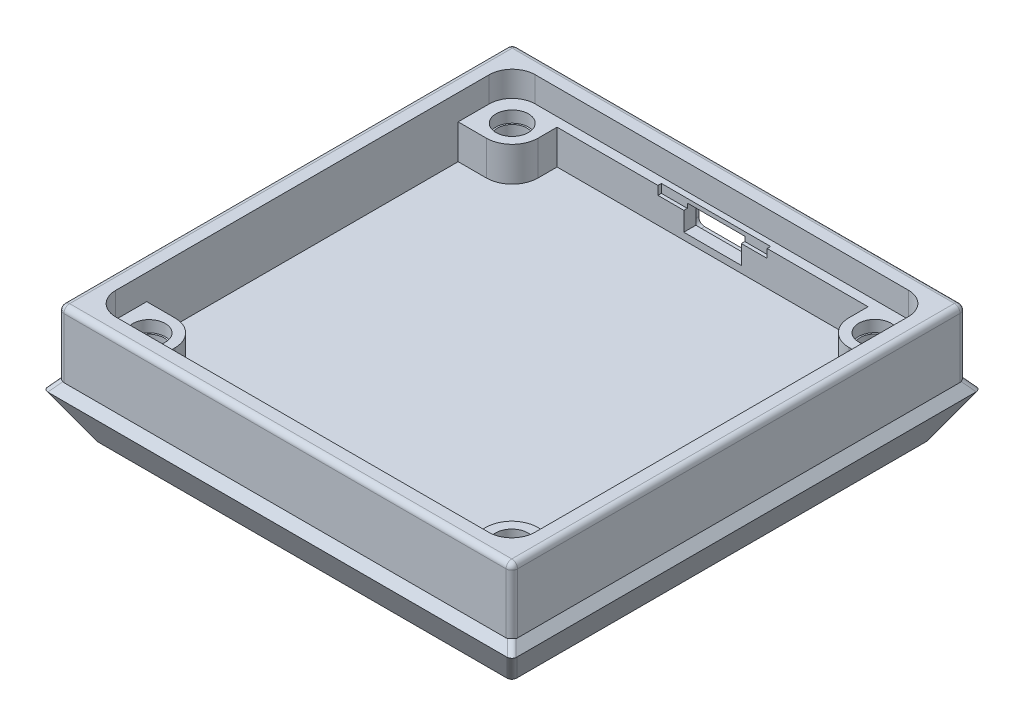
SolidWorks part; units mm, degrees
ref_plane "Front Plane" through (0, 0, 0) normal (0, 0, 1) x (1, 0, 0)
ref_plane "Top Plane" through (0, 0, 0) normal (0, 1, 0) x (1, 0, 0)
ref_plane "Right Plane" through (0, 0, 0) normal (1, 0, 0) x (0, 0, -1)
sketch "Sketch1" plane through (0, 0, 0) normal (0, 1, 0) x (1, 0, 0)
  line L0 (-34.54, 34.575) -> (-34.54, 36.475) construction
  line L1 (-34.54, -34.575) -> (34.54, -34.575)
  line L2 (-34.54, -34.575) -> (-34.54, 34.575)
  line L3 (-34.54, 34.575) -> (34.54, 34.575)
  line L4 (34.54, -34.575) -> (34.54, 34.575)
  line L5 (-34.54, -34.575) -> (34.54, 34.575) construction
  line L6 (-34.54, 34.575) -> (34.54, -34.575) construction
  line L7 (-34.54, 36.475) -> (-36.44, 36.475) construction
  line L8 (34.54, -34.575) -> (36.44, -34.575) construction
  line L9 (36.44, -34.575) -> (36.44, -36.475) construction
  line L11 (-36.44, 36.475) -> (36.44, 36.475)
  line L12 (-36.44, 36.475) -> (-36.44, -36.475)
  line L13 (-36.44, -36.475) -> (36.44, -36.475)
  line L14 (36.44, 36.475) -> (36.44, -36.475)
  point P0 (0, 0)
  dimension "D1" = 69.15
  dimension "D2" = 69.08
  dimension "D3" = 1.9
  dimension "D4" = 1.9
  dimension "D5" = 1.9
  dimension "D6" = 1.9
extrude "floor" add sketch "Sketch1" along normal blind 10 contours L14 L11 L12 L13 L4 L1 L2 L3 | L1 L4 L3 L2 region at (0, 0, 0) region at (0, 0, -35.4438)
sketch "Sketch3" plane through (0, 0, 0) normal (0, -1, 0) x (1, 0, 0)
  line L0 (36.44, 36.475) -> (39.44, 36.475) construction
  line L1 (39.44, 36.475) -> (39.44, 39.475) construction
  line L2 (-36.44, -36.475) -> (-39.44, -36.475) construction
  line L3 (-39.44, -36.475) -> (-39.44, -39.475) construction
  line L5 (-39.44, -39.475) -> (39.44, -39.475)
  line L6 (-39.44, -39.475) -> (-39.44, 39.475)
  line L7 (-39.44, 39.475) -> (39.44, 39.475)
  line L8 (39.44, -39.475) -> (39.44, 39.475)
  line L9 (-36.44, 36.475) -> (36.44, 36.475)
  line L10 (-36.44, 36.475) -> (-36.44, -36.475)
  line L11 (-36.44, -36.475) -> (36.44, -36.475)
  line L12 (36.44, 36.475) -> (36.44, -36.475)
  dimension "D1" = 3
  dimension "D2" = 3
  dimension "D3" = 3
  dimension "D4" = 3
extrude "walls from bottom" add sketch "Sketch3" against normal blind 20.4
sketch "Sketch4" plane through (0, 10, 0) normal (0, 1, 0) x (1, 0, 0)
  line L0 (-34.5375, 34.575) -> (-31.5375, 34.575) construction
  line L1 (-34.5375, -34.575) -> (34.5375, -34.575) construction
  line L2 (-34.5375, -34.575) -> (-34.5375, 34.575) construction
  line L3 (-34.5375, 34.575) -> (34.5375, 34.575) construction
  line L4 (34.5375, -34.575) -> (34.5375, 34.575) construction
  line L5 (-34.5375, -34.575) -> (34.5375, 34.575) construction
  line L6 (-34.5375, 34.575) -> (34.5375, -34.575) construction
  line L7 (-31.5375, 34.575) -> (-31.5375, 31.575) construction
  line L8 (34.5375, -34.575) -> (31.5375, -34.575) construction
  line L9 (31.5375, -34.575) -> (31.5375, -31.575) construction
  line L10 (-31.5375, -27.075) -> (-36.44, -27.075)
  line L11 (-31.5375, 31.575) -> (31.5375, 31.575) construction
  line L12 (-31.5375, 31.575) -> (-31.5375, -31.575) construction
  line L13 (-31.5375, -31.575) -> (31.5375, -31.575) construction
  line L14 (31.5375, 31.575) -> (31.5375, -31.575) construction
  line L15 (-36.44, -36.475) -> (-36.44, 36.475) construction
  line L16 (-27.0375, 31.575) -> (-27.0375, 36.475)
  line L17 (36.44, -36.475) -> (-36.44, -36.475) construction
  line L18 (-36.44, 36.475) -> (36.44, 36.475) construction
  line L19 (31.5375, -27.075) -> (36.44, -27.075)
  line L22 (31.5375, 27.075) -> (36.44, 27.075)
  line L23 (36.44, 36.475) -> (36.44, -36.475) construction
  line L24 (-27.0375, 36.475) -> (-31.5375, 36.475)
  line L25 (-36.44, 36.475) -> (36.44, 36.475) construction
  line L26 (-31.5375, 27.075) -> (-36.44, 27.075)
  line L27 (27.0375, 31.575) -> (27.0375, 36.475)
  line L28 (-36.44, 27.075) -> (-36.44, 36.475)
  line L29 (-36.44, 36.475) -> (-31.5375, 36.475)
  line L30 (31.5375, 36.475) -> (36.44, 36.475)
  line L31 (36.44, 36.475) -> (36.44, 27.075)
  line L32 (31.5375, -36.475) -> (36.44, -36.475)
  line L33 (36.44, -36.475) -> (36.44, -27.075)
  line L34 (-36.44, -27.075) -> (-36.44, -36.475)
  line L35 (-27.0375, -36.475) -> (-36.44, -36.475)
  line L36 (27.0375, 36.475) -> (31.5375, 36.475)
  line L37 (27.0375, -31.575) -> (27.0375, -36.475)
  line L40 (27.0375, -36.475) -> (31.5375, -36.475)
  line L41 (-27.0375, -31.575) -> (-27.0375, -36.475)
  circle A8 centre (-31.5375, 31.575) radius 2.55
  circle A9 centre (31.5375, 31.575) radius 4.5
  circle A10 centre (31.5375, -31.575) radius 2.55
  circle A11 centre (-31.5375, -31.575) radius 4.5
  circle A12 centre (-31.5375, -31.575) radius 2.55
  circle A13 centre (-31.5375, 31.575) radius 4.5
  circle A14 centre (31.5375, -31.575) radius 4.5
  circle A15 centre (31.5375, 31.575) radius 2.55
  point P0 (0, 0)
  line M5 (36.44, -36.475) -> (36.44, 36.475)
  line M6 (36.44, 36.475) -> (-36.44, 36.475)
  line M7 (-36.44, 36.475) -> (-36.44, -36.475)
  line M8 (-36.44, -36.475) -> (36.44, -36.475)
  dimension "D3" = 3
  dimension "D4" = 3
  dimension "D7" = 5.1
  dimension "D8" = 9
  dimension "D9" = 5.1
  dimension "D10" = 9
  dimension "D11" = 5.1
  dimension "D12" = 9
  dimension "D13" = 5.1
  dimension "D14" = 9
  dimension "D1" = 69.075
  dimension "D2" = 69.15
  dimension "D5" = 3
  dimension "D6" = 3
extrude "Boss-Extrude1" add sketch "Sketch4" along normal blind 6 contours A13 L26 M6 M7 | A9 L22 M5 M6 | A14 L19 M8 M5 | A11 L10 M7 M8 | A11 A12 | A13 A8 | A9 A15 | A14 A10 region at (-34.8135, 10, 34.851) region at (-28.4455, 10, 28.483) region at (-36.307, 10, -31.775) region at (-34.6295, 10, -34.667) region at (27.1705, 10, 34.025) region at (28.4455, 10, 28.483) region at (29.2875, 10, -36.342) region at (31.5375, 10, -35.9477)
sketch "Sketch21" plane through (0, 16, 0) normal (0, 1, 0) x (1, 0, 0)
  circle A0 centre (-31.5375, 31.575) radius 2.825
  circle A1 centre (31.5375, 31.575) radius 2.825
  circle A2 centre (-31.5375, -31.575) radius 2.825
  circle A3 centre (31.5375, -31.575) radius 2.825
  dimension "D1" = 5.65
  dimension "D2" = 5.65
  dimension "D3" = 5.65
  dimension "D4" = 5.65
extrude "Cut-Extrude9" cut sketch "Sketch21" against normal blind 2
sketch "Sketch7" plane through (0, 16, 0) normal (0, 1, 0) x (1, 0, 0)
  line L0 (-31.5375, 31.575) -> (-31.5375, 34.575) construction
  line L1 (-31.5375, 34.575) -> (-31.5375, 34.875) construction
  line L2 (-31.5375, 34.875) -> (31.5375, 34.875) construction
  line L3 (31.5375, 31.575) -> (31.5375, 34.875) construction
  line L4 (-27.0375, 36.475) -> (-27.0375, 34.875)
  line L5 (-27.0375, 31.575) -> (-27.0375, 36.475) construction
  line L6 (27.0375, 36.475) -> (27.0375, 34.875)
  line L7 (27.0375, 31.575) -> (27.0375, 36.475) construction
  line L8 (-27.0375, 34.875) -> (27.0375, 34.875)
  line L9 (-27.0375, 36.475) -> (27.0375, 36.475)
  dimension "D1" = 3
  dimension "D2" = 0.3
extrude "Boss-Extrude2" add sketch "Sketch7" against normal up to surface (6 mm away) up to face at (0, 10, 0)
sketch "Sketch8" plane through (0, 16, 0) normal (0, 1, 0) x (1, 0, 0)
  line L0 (-36.44, 36.475) -> (36.44, 36.475) construction
  line L1 (0, 36.475) -> (0, 34.875) construction
  line L2 (27.0375, 34.875) -> (-27.0375, 34.875) construction
  line L3 (0, 34.875) -> (-5, 34.875)
  line L5 (0, 34.875) -> (5, 34.875)
  line L6 (-5, 34.875) -> (-5, 36.475)
  line L7 (-5, 36.475) -> (0, 36.475)
  line L8 (0, 36.475) -> (5, 36.475)
  line L9 (5, 36.475) -> (5, 34.875)
  point P11 (0, 34.875)
  point P13 (0, 35.575)
  dimension "D1" = 5
  dimension "D2" = 5
extrude "Cut-Extrude1" cut sketch "Sketch8" against normal blind 4.8 contours L9 L5 L3 L6 L7 L8
sketch "Sketch9" plane through (0, 0, -36.475) normal (0, 0, 1) x (1, 0, 0)
  line L0 (0, 11.2) -> (0, 15.3) construction
  line L1 (-5, 11.2) -> (5, 11.2) construction
  line L2 (0, 15.3) -> (-5, 15.3)
  line L3 (-5, 11.2) -> (-5, 16) construction
  line L4 (0, 15.3) -> (5, 15.3)
  line L5 (5, 11.2) -> (5, 16) construction
  line L6 (-5, 15.3) -> (-5, 11.2)
  line L7 (-5, 11.2) -> (5, 11.2)
  line L8 (5, 11.2) -> (5, 15.3)
  dimension "D1" = 4.1
extrude "Cut-Extrude2" cut sketch "Sketch9" against normal through all
sketch "Sketch10" plane through (0, 16, 0) normal (0, 1, 0) x (1, 0, 0)
  line L0 (-5, 34.875) -> (-5, 36.475) construction
  line L1 (-5, 34.875) -> (-9.5, 34.875)
  line L2 (-5, 34.875) -> (-5, 36.475)
  line L3 (-5, 36.475) -> (-9.5, 36.475)
  line L4 (-9.5, 34.875) -> (-9.5, 36.475)
  line L5 (-27.0375, 34.875) -> (-5, 34.875) construction
  line L6 (-36.44, 36.475) -> (36.44, 36.475) construction
  line L7 (36.44, 36.475) -> (5, 36.475) construction
  line L8 (5, 34.875) -> (9.5, 34.875)
  line L9 (5, 34.875) -> (5, 36.475)
  line L10 (5, 36.475) -> (9.5, 36.475)
  line L11 (9.5, 34.875) -> (9.5, 36.475)
  dimension "D1" = 4.5
  dimension "D2" = 4.5
extrude "Cut-Extrude3" cut sketch "Sketch10" against normal blind 1.5
sketch "Sketch11" plane through (0, 0, -39.475) normal (0, 0, -1) x (-1, 0, 0)
  line L0 (-5, 15.3) -> (5, 11.2) construction
  line L1 (5, 15.3) -> (-5, 11.2) construction
  line L2 (0, 9.25) -> (0, 17.25) construction
  line L3 (-6, 17.25) -> (6, 17.25)
  line L4 (-6, 9.25) -> (6, 9.25)
  line L5 (-7, 16.25) -> (-7, 10.25)
  line L6 (7, 16.25) -> (7, 10.25)
  arc A0 (-6, 9.25) -> (-7, 10.25) centre (-6, 10.25) cw
  arc A1 (6, 9.25) -> (7, 10.25) centre (6, 10.25) ccw
  arc A2 (6, 17.25) -> (7, 16.25) centre (6, 16.25) cw
  arc A3 (-6, 17.25) -> (-7, 16.25) centre (-6, 16.25) ccw
  point P12 (0, 13.25)
  point P15 (0, 17.25)
  point P18 (0, 9.25)
  point P20 (-7, 9.25)
  point P23 (7, 9.25)
  point P26 (7, 17.25)
  dimension "D3" = 1
  dimension "D1" = 8
  dimension "D2" = 14
extrude "Cut-Extrude4" cut sketch "Sketch11" against normal blind 2.5
sketch "Sketch16" plane through (0, 0, -39.475) normal (0, 0, -1) x (-1, 0, 0)
  line L0 (-39.44, 20.4) -> (-39.44, 0) construction
  line L1 (39.44, 0) -> (39.44, 20.4) construction
  line L2 (-39.44, 9) -> (-46.665, 9)
  line L3 (-46.665, 9) -> (-46.665, 0)
  line L4 (-46.665, 0) -> (44.9933, 0)
  line L5 (44.9933, 0) -> (44.9933, 9)
  line L6 (44.9933, 9) -> (-39.44, 9)
  line L7 (-39.44, 20.4) -> (-39.44, 0) construction
  dimension "D1" = 9
extrude "Boss-Extrude7" add sketch "Sketch16" against normal blind 87
sketch "Sketch17" plane through (46.665, 0, 0) normal (1, 0, 0) x (0, 0, -1)
  line L1 (39.475, 0) -> (43.2265, 0)
  line L2 (39.475, 0) -> (39.475, 9)
  line L3 (39.475, 9) -> (43.2265, 9)
  line L4 (43.2265, 0) -> (43.2265, 9)
extrude "Boss-Extrude8" add sketch "Sketch17" against normal up to surface (91.6583 mm away) up to face at (-44.9933, 4.5, 4.025)
sketch "Sketch19" plane through (0, 0, -43.2265) normal (0, 0, -1) x (-1, 0, 0)
  line L0 (-39.44, 9) -> (-40.7256, 7.4679)
  line L1 (-40.7256, 7.4679) -> (-36.414, 0)
  line L2 (44.9933, 0) -> (-46.665, 0) construction
  line L3 (-39.44, 20.4) -> (-39.44, 9) construction
  line L4 (-36.414, 0) -> (-50.6273, 0)
  line L5 (-50.6273, 0) -> (-50.6273, 9)
  line L6 (-50.6273, 9) -> (-39.44, 9)
  line L7 (39.44, 9) -> (40.7256, 7.4679)
  line L8 (40.7256, 7.4679) -> (36.414, 0)
  line L9 (39.44, 20.4) -> (39.44, 9) construction
  line L10 (36.414, 0) -> (59.329, 0)
  line L11 (59.329, 0) -> (59.329, 9)
  line L12 (59.329, 9) -> (39.44, 9)
  dimension "D1" = 2
  dimension "D2" = 140
  dimension "D3" = 110
  dimension "D4" = 140
  dimension "D5" = 110
  dimension "D6" = 2
extrude "Cut-Extrude7" cut sketch "Sketch19" against normal through all both
sketch "Sketch20" plane through (39.44, 0, 0) normal (1, 0, 0) x (0, 0, -1)
  line L0 (-39.475, 9) -> (-40.7606, 7.4679)
  line L1 (-47.525, 7.4679) -> (43.2265, 7.4679) construction
  line L2 (-40.7606, 7.4679) -> (-36.449, 0)
  line L3 (-47.525, 0) -> (43.2265, 0) construction
  line L4 (-39.475, 20.4) -> (-39.475, 9) construction
  line L5 (39.475, 9) -> (40.7606, 7.4679)
  line L6 (40.7606, 7.4679) -> (36.449, 0)
  line L7 (39.475, 20.4) -> (39.475, 9) construction
  line L8 (-36.449, 0) -> (-51.4465, 0)
  line L9 (-51.4465, 0) -> (-51.4465, 9)
  line L10 (-51.4465, 9) -> (-39.475, 9)
  line L11 (39.475, 9) -> (51.5191, 9)
  line L12 (51.5191, 9) -> (51.5191, 0)
  line L13 (51.5191, 0) -> (36.449, 0)
  dimension "D1" = 140
  dimension "D2" = 110
  dimension "D3" = 140
  dimension "D4" = 110
extrude "Cut-Extrude8" cut sketch "Sketch20" against normal through all both and the other way blind 39
fillet "Fillet1" radius 4 4 edges at (-36.44, 18.2, 36.475) (36.44, 18.2, 36.475) (36.44, 18.2, -36.475) (-36.44, 18.2, -36.475)
fillet "Fillet2" radius 1 12 edges at (38.5698, 3.734, -38.6048) (40.0828, 8.234, -40.1178) (39.44, 14.7, -39.475) (-39.44, 14.7, -39.475) (-40.0828, 8.234, -40.1178) (-38.5698, 3.734, -38.6048) (-38.5698, 3.734, 38.6048) (-40.0828, 8.234, 40.1178) (38.5698, 3.734, 38.6048) (40.0828, 8.234, 40.1178) (39.44, 14.7, 39.475) (-39.44, 14.7, 39.475)
fillet "Fillet3" radius 1 8 edges at (39.1471, 20.4, 39.1821) (39.44, 20.4, 0) (39.1471, 20.4, -39.1821) (0, 20.4, -39.475) (-39.1471, 20.4, -39.1821) (-39.44, 20.4, 0) (-39.1471, 20.4, 39.1821) (0, 20.4, 39.475)
sketch "plate export" plane through (0, 16, 0) normal (0, 1, 0) x (1, 0, 0)
  line L12 (-36.54, 32.575) -> (-36.54, -32.575)
  line L13 (32.54, -36.575) -> (-32.54, -36.575)
  line L14 (36.54, 32.575) -> (36.54, -32.575)
  line L15 (32.54, 36.575) -> (-32.54, 36.575)
  line L16 (0, -36.575) -> (0, -27.2079)
  line L17 (-7.4554, -27.2079) -> (7.4554, -27.2079)
  line L18 (-7.4554, -10.6929) -> (7.4554, -10.6929)
  line L19 (-7.4554, -10.6929) -> (-7.4554, -27.2079)
  line L20 (7.4554, -10.6929) -> (7.4554, -27.2079)
  line L21 (-7.4554, -18.9504) -> (-11.7304, -18.9504) construction
  line L22 (-7.4554, -10.6929) -> (-11.7304, -10.6929) construction
  line L23 (-7.4554, -27.2079) -> (-11.7304, -27.2079) construction
  line L24 (7.4554, -10.6929) -> (11.7491, -10.6929) construction
  line L25 (-11.7304, -27.2079) -> (-26.5137, -27.2079)
  line L26 (-11.7304, -27.2079) -> (-11.7304, -10.6929)
  line L27 (-11.7304, -10.6929) -> (-26.5137, -10.6929)
  line L28 (-26.5137, -27.2079) -> (-26.5137, -10.6929)
  line L29 (7.4554, -27.2079) -> (11.7491, -27.2079) construction
  line L30 (11.7491, -10.6929) -> (11.7491, -8.1385) construction
  line L31 (11.7491, -27.2079) -> (26.3694, -27.2079)
  line L32 (11.7491, -27.2079) -> (11.7491, -10.6929)
  line L33 (11.7491, -10.6929) -> (26.3694, -10.6929)
  line L34 (26.3694, -27.2079) -> (26.3694, -10.6929)
  line L35 (26.3694, -10.6929) -> (26.3694, -8.1385) construction
  line L36 (7.4554, -10.6929) -> (7.4554, -8.1385) construction
  line L37 (11.7491, -8.1385) -> (26.3694, -8.1385)
  line L38 (11.7491, -8.1385) -> (11.7491, 8.1667)
  line L39 (11.7491, 8.1667) -> (26.3694, 8.1667)
  line L40 (26.3694, -8.1385) -> (26.3694, 8.1667)
  line L41 (-26.5137, -10.6929) -> (-26.5137, -8.1385) construction
  line L42 (-11.7304, -10.6929) -> (-11.7304, -8.1385) construction
  line L43 (-11.7304, -8.1385) -> (-7.4554, -8.1385) construction
  line L44 (-26.5137, -8.1385) -> (-11.7304, -8.1385)
  line L45 (-26.5137, -8.1385) -> (-26.5137, 8.1667)
  line L46 (-26.5137, 8.1667) -> (-11.7304, 8.1667)
  line L47 (-11.7304, -8.1385) -> (-11.7304, 8.1667)
  line L48 (11.7491, 8.1667) -> (7.4554, 8.1667) construction
  line L49 (21.5375, 11.575) -> (21.5375, 11.275) construction
  line L50 (-7.4554, -8.1385) -> (7.4554, -8.1385)
  line L51 (-7.4554, -8.1385) -> (-7.4554, 8.1667)
  line L52 (-7.4554, 8.1667) -> (7.4554, 8.1667)
  line L53 (7.4554, -8.1385) -> (7.4554, 8.1667)
  line L54 (21.5375, 11.275) -> (25.6875, 11.275) construction
  line L55 (25.3875, 19.075) -> (25.6875, 19.075) construction
  line L56 (-25.7125, 27.7874) -> (-31.5375, 27.7874) construction
  line L57 (25.6875, 19.075) -> (25.6875, 11.275) construction
  line L58 (25.3875, 19.725) -> (25.3875, 18.425) construction
  line L59 (-21.5625, 12.1) -> (-21.5625, 11.8) construction
  line L60 (25.6875, 11.275) -> (12.4598, 11.275)
  line L61 (25.6875, 11.275) -> (25.6875, 27.189)
  line L62 (25.6875, 27.189) -> (12.4598, 27.189)
  line L63 (12.4598, 11.275) -> (12.4598, 27.189)
  line L64 (-25.4125, 19.6) -> (-25.7125, 19.6) construction
  line L65 (-25.4125, 18.95) -> (-25.4125, 20.25) construction
  line L66 (-25.7125, 19.6) -> (-25.7125, 11.8) construction
  line L67 (-25.7125, 11.8) -> (-21.5625, 11.8) construction
  line L68 (-31.5375, 27.7874) -> (-31.5375, 31.575) construction
  line L69 (-25.7125, 11.8) -> (-12.5037, 11.8)
  line L70 (-25.7125, 11.8) -> (-25.7125, 27.7874)
  line L71 (-25.7125, 27.7874) -> (-12.5037, 27.7874)
  line L72 (-12.5037, 11.8) -> (-12.5037, 27.7874)
  line L73 (-31.5375, 31.575) -> (31.5375, 31.575) construction
  circle A0 centre (21.5375, 12.075) radius 0.5 construction
  circle A1 centre (-21.5625, 12.6) radius 0.5 construction
  arc A2 (-32.54, -36.575) -> (-36.54, -32.575) centre (-32.54, -32.575) cw
  arc A3 (36.54, -32.575) -> (32.54, -36.575) centre (32.54, -32.575) cw
  arc A4 (32.54, 36.575) -> (36.54, 32.575) centre (32.54, 32.575) cw
  arc A5 (-36.54, 32.575) -> (-32.54, 36.575) centre (-32.54, 32.575) cw
  point P12 (0, -27.2079)
  point P17 (0, -10.6929)
  dimension "D1" = 4
sketch "Sketch22" plane through (0, 0, -36.475) normal (0, 0, 1) x (1, 0, 0)
  line L0 (-9.5, 16) -> (9.5, 16)
  line L1 (9.5, 16) -> (9.5, 14.5)
  line L2 (9.5, 14.5) -> (5, 14.5)
  line L3 (5, 14.5) -> (5, 15.3)
  line L4 (5, 15.3) -> (-5, 15.3)
  line L5 (-5, 15.3) -> (-5, 14.5)
  line L6 (-5, 14.5) -> (-9.5, 14.5)
  line L7 (-9.5, 14.5) -> (-9.5, 16)
extrude "Boss-Extrude9" add sketch "Sketch22" along normal blind 1
equation "\"D4@Sketch1\"= \"D3@Sketch1\""
equation "\"D5@Sketch1\"=\"D3@Sketch1\""
equation "\"D6@Sketch1\"=\"D3@Sketch1\""
equation "\"D2@Sketch3\"=\"D1@Sketch3\""
equation "\"D3@Sketch3\"=\"D1@Sketch3\""
equation "\"D4@Sketch3\"=\"D1@Sketch3\""
equation "\"D9@Sketch4\"=\"D7@Sketch4\""
equation "\"D10@Sketch4\"=\"D8@Sketch4\""
equation "\"D11@Sketch4\"=\"D7@Sketch4\""
equation "\"D12@Sketch4\"=\"D8@Sketch4\""
equation "\"D13@Sketch4\"=\"D7@Sketch4\""
equation "\"D14@Sketch4\"=\"D8@Sketch4\""
equation "\"D1@Cut-Extrude1\"=4.8"
equation "\"D2@Sketch10\"= \"D1@Sketch10\""
equation "\"D2@Sketch8\"=\"D1@Sketch8\""
equation "\"D1@walls from bottom\"=16+1.6+1.5+1.3"
equation "\"D2@Sketch21\"=\"D1@Sketch21\""
equation "\"D3@Sketch21\"=\"D1@Sketch21\""
equation "\"D4@Sketch21\"=\"D1@Sketch21\""
